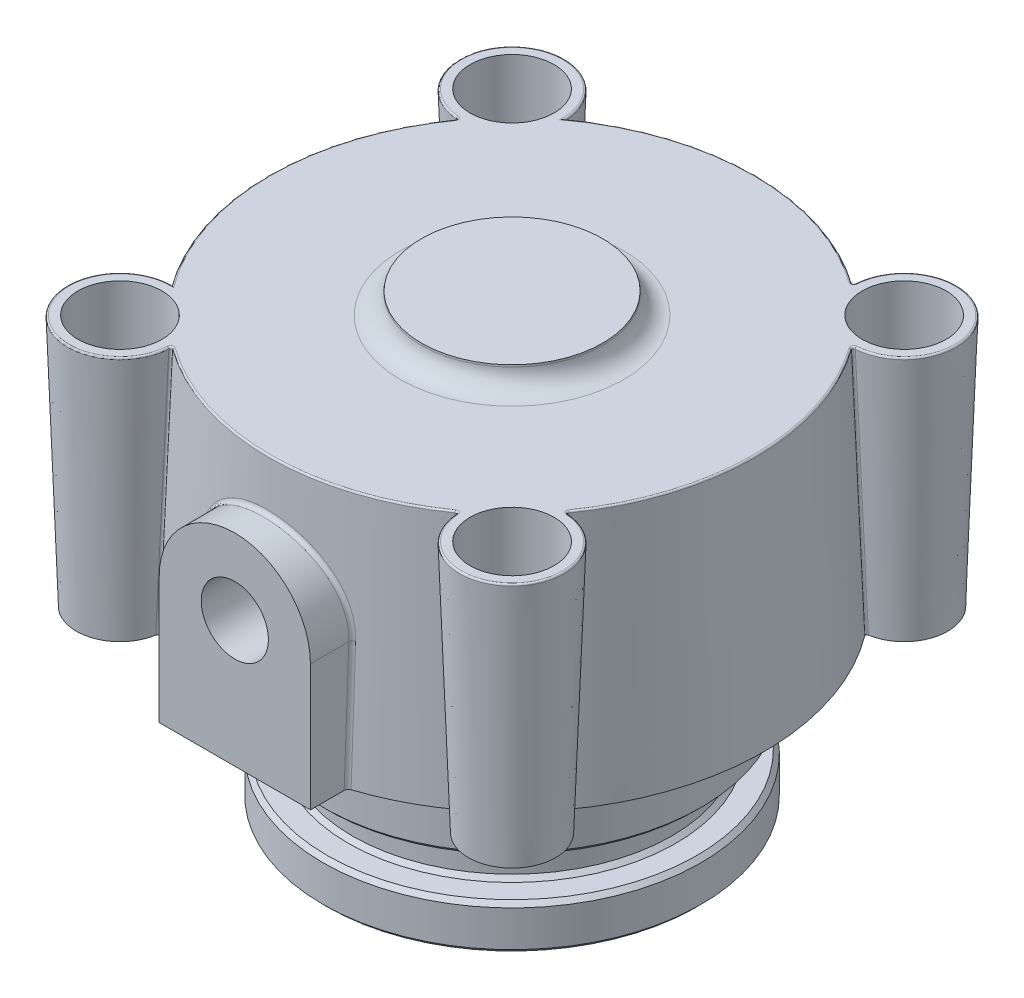
SolidWorks part; units mm, degrees
note: The reader was unsure of these and kept them because the rebuilt part matched: shared geometry of "Sketch8<4>", "Sketch8<5>", "Croquis17<2>", "Croquis1<2>".
material "Aleación 1060"
ref_plane "Front Plane" through (0, 0, 0) normal (0, 0, 1) x (1, 0, 0)
ref_plane "Top Plane" through (0, 0, 0) normal (0, 1, 0) x (1, 0, 0)
ref_plane "Right Plane" through (0, 0, 0) normal (1, 0, 0) x (0, 0, -1)
sketch "Sketch1" plane through (0, 0, 0) normal (0, 1, 0) x (1, 0, 0)
  circle A0 centre (0, 0) radius 22.5
  dimension "D1" = 45
extrude "Boss-Extrude1" add sketch "Sketch1" along normal blind 20
sketch "Sketch2" plane through (0, 20, 0) normal (0, 1, 0) x (1, 0, 0)
  circle A0 centre (0, 0) radius 30
  point P14 (0, 0)
  point P19 (0, 0)
  dimension "D1" = 60
extrude "Boss-Extrude2" add sketch "Sketch2" along normal blind 30 draft 2
sketch "Sketch3" plane through (0, 50, 0) normal (0, 1, 0) x (1, 0, 0)
  circle A0 centre (0, 0) radius 11
  dimension "D1" = 22
extrude "Boss-Extrude3" add sketch "Sketch3" along normal blind 2.5 draft 5 and the other way blind 40
ref_plane "Plane1" through (0, 0, 23) normal (0, 0, 1) x (1, 0, 0)
sketch "Sketch8" plane through (0, 0, 23) normal (0, 0, 1) x (1, 0, 0)
  line L3 (-9, 35.0488) -> (-9, 20)
  line L6 (0, -55) -> (0, 55) construction
  line L7 (28.9524, 50) -> (-28.9524, 50) construction
  line L10 (-22.5, 20) -> (22.5, 20) construction
  line L11 (-9, 20) -> (9, 20)
  line L12 (9, 20) -> (9, 35.0488)
  line L13 (-9, 20) -> (9, 20)
  arc A0 (-9, 35.0488) -> (9, 35.0488) centre (0, 35.0488) cw
  circle A1 centre (0, 35.0488) radius 4
  dimension "D3" = 9
  dimension "D4" = 8
  dimension "D1" = 18
  dimension "D6" = 14.9512
sketch "Croquis1" plane through (0, 52.5, 0) normal (0, 1, 0) x (1, 0, 0)
  circle A0 centre (0, 0) radius 8
  dimension "D1" = 16
extrude "Cortar-Extruir1" cut sketch "Croquis1" against normal blind 90
sketch "Croquis2" plane through (0, 52.5, 0) normal (0, 1, 0) x (1, 0, 0)
  circle A0 centre (0, 0) radius 9
  dimension "D1" = 18
sketch "Croquis3" plane through (0, 50, 0) normal (0, 1, 0) x (1, 0, 0)
  line L0 (0, 0) -> (-35.3676, 35.3676) construction
  line L1 (0, 0) -> (35.2874, -35.2874) construction
  line L2 (0, 0) -> (35.299, 35.299) construction
  line L3 (0, 0) -> (-35.4361, -35.4361) construction
  circle A9 centre (-23.3345, 23.3345) radius 6.235
  circle A12 centre (-23.3345, 23.3345) radius 5
  point P7 (-23.3345, 23.3345)
  point P9 (-21.2132, -21.2132)
  point P12 (21.2132, -21.2132)
  point P13 (-23.3345, 23.3345)
  point P14 (21.2132, 21.2132)
  circle M5 centre (0, 0) radius 28.9524
  dimension "D3" = 90
  dimension "D1" = 12.47
  dimension "D2" = 90
  dimension "D5" = 10
  dimension "D6" = 33
extrude "Saliente-Extruir1" add sketch "Croquis3" against normal blind 30 draft 2 contours A9 M5 | A9 A12 M5 | A12
pattern_circular "MatrizC1" count 4 over 360 about axis through (0, 0, 0) along (0, 1, 0) of "Saliente-Extruir1"
extrude "Saliente-Extruir2" add sketch "Sketch8" along normal blind 10 contours L12 A0 L3 L11 | A1
pattern_circular "MatrizC2" count 2 over 360 about axis through (0, 0, 0) along (0, 1, 0) of "Saliente-Extruir2"
cosmetic thread "Rosca cosmética1" parameters "D1"=15, "D2"=10
sketch "Croquis10" plane through (0, 0, 23) normal (0, 0, 1) x (1, 0, 0)
  circle A0 centre (0, 35.0488) radius 3.9079
ref_plane "Plano1" through (0, 0, -37) normal (0, 0, -1) x (-1, 0, 0)
sketch "Croquis11" plane through (0, 0, -37) normal (0, 0, -1) x (-1, 0, 0)
  circle A0 centre (0, 35.0488) radius 4
extrude "Cortar-Extruir5" cut sketch "Croquis11" against normal blind 40
sketch "Croquis12" plane through (0, 0, 0) normal (1, 0, 0) x (0, 0, -1)
  line L0 (-22.5, 10) -> (-19, 10)
  line L1 (-22.5, 20) -> (-22.5, 0) construction
  line L2 (-19, 10) -> (-19, 5.3)
  line L3 (-19, 5.3) -> (-22.5, 5.3)
  line L4 (0, 0) -> (0, 52.5) construction
  line L5 (9, 52.5) -> (-9, 52.5) construction
  line L6 (-22.5, 10) -> (-22.5, 5.3)
  dimension "D1" = 4.7
  dimension "D2" = 3.5
revolve "Cortar-Revolución1" cut sketch "Croquis12" angle 360 about L4
sketch "Croquis13" plane through (0, 0, 0) normal (1, 0, 0) x (0, 0, -1)
  line L0 (0.0017, 13.7509) -> (-11.9983, 13.7509)
  line L1 (-11.9983, 13.7509) -> (-11.9983, 17.8541)
  line L2 (-11.9983, 17.8541) -> (0.0017, 17.8541)
  line L3 (0.0017, 17.8541) -> (0.0017, 13.7509)
  line L5 (0, 0) -> (0, 52.5) construction
  line L6 (9, 52.5) -> (-9, 52.5) construction
  line L7 (0.0017, 17.8541) -> (0.0017, 13.7509)
  dimension "D1" = 4.1033
  dimension "D2" = 12
revolve "Cortar-Revolución3" cut sketch "Croquis13" angle 360 about L3
extrude "Cortar-Extruir7" cut sketch "Sketch8<4>" along normal blind 7 contours A1
sketch "Sketch8<4>" plane through (0, 0, 23) normal (0, 0, 1) x (1, 0, 0) same geometry as "Sketch8"
extrude "Cortar-Extruir8" cut sketch "Sketch8<5>" against normal blind 0.2 contours A1
sketch "Sketch8<5>" plane through (0, 0, 23) normal (0, 0, 1) x (1, 0, 0) same geometry as "Sketch8"
sketch "Croquis16" plane through (0, 0, 0) normal (0, -1, 0) x (1, 0, 0)
  circle A0 centre (0, 14.3104) radius 3
  point P0 (0, 14.3104)
  dimension "D1" = 6
extrude "Cortar-Extruir9" cut sketch "Croquis16" against normal blind 34
ref_plane "Plano2" through (0, 0, 15) normal (0, 0, 1) x (1, 0, 0)
sketch "Croquis17" plane through (0, 0, 15) normal (0, 0, 1) x (1, 0, 0)
  circle A0 centre (0, 35.0488) radius 3.5
  dimension "D1" = 7
extrude "Cortar-Extruir10" cut sketch "Croquis17" along normal blind 8
cosmetic thread "Rosca cosmética10" parameters "D1"=5, "D2"=7.513
extrude "Cortar-Extruir11" cut sketch "Croquis17<2>" against normal blind 0.2
sketch "Croquis17<2>" plane through (0, 0, 15) normal (0, 0, 1) x (1, 0, 0) same geometry as "Croquis17"
ref_plane "Plano3" through (0, 0, 13) normal (0, 0, 1) x (1, 0, 0)
sketch "Croquis18" plane through (0, 0, 13) normal (0, 0, 1) x (1, 0, 0)
  circle A0 centre (0, 35.0488) radius 3
  dimension "D1" = 6
extrude "Cortar-Extruir12" cut sketch "Croquis18" along normal blind 8
sketch "Croquis19" plane through (0, 0, 0) normal (0, 0, 1) x (1, 0, 0)
  circle A0 centre (0, 35.0488) radius 2.5
  dimension "D1" = 5
extrude "Cortar-Extruir13" cut sketch "Croquis19" along normal blind 20
sketch "Croquis21" plane through (0, 50, 0) normal (0, 1, 0) x (1, 0, 0)
  circle A0 centre (-23.3345, 23.3345) radius 5
  circle A1 centre (-23.3345, 23.3345) radius 2.5
  point P0 (-23.3345, 23.3345)
  point P3 (25.8804, 25.8804)
  point P5 (28.4263, -23.3345)
  point P7 (-20.7886, -25.8804)
  point P10 (2.5459, 0)
  dimension "D2" = 10
  dimension "D1" = 4
extrude "Cortar-Extruir14" cut sketch "Croquis21" against normal blind 10 contours A1 | A0 A1
pattern_circular "MatrizC3" count 4 over 360 about axis through (0, 0, 0) along (0, 1, 0) of "Cortar-Extruir14"
fillet "Redondeo8" radius 0.2 14 edges at (-28.9524, 50, 0) (-23.5243, 40.7577, -17.4253) (-27.7433, 50, -27.7433) (0, 50, 28.9524) (28.9524, 50, 0) (0, 50, -28.9524) (-17.4253, 40.7577, 23.5243) (-27.7433, 50, 27.7433) (23.5243, 40.7577, 17.4253) (17.9257, 26.8144, 23.7581) (27.7433, 50, 27.7433) (17.4253, 40.7577, -23.5243) (23.7581, 26.8144, -17.9257) (27.7433, 50, -27.7433)
chamfer "Chaflán1" distance 0.25 angle 45 1 edges at (0, 38.0488, 14.8)
sketch "Croquis24" plane through (0, 50, 0) normal (0, 1, 0) x (1, 0, 0)
  circle A0 centre (-23.3345, 23.3345) radius 3
  point P0 (-23.3345, 23.3345)
  dimension "D1" = 6
extrude "Cortar-Extruir16" cut sketch "Croquis24" against normal blind 30
sketch "Croquis25" plane through (0, 50, 0) normal (0, 1, 0) x (1, 0, 0)
  circle A1 centre (-23.3345, -23.3345) radius 3
  circle A2 centre (23.3345, -23.3345) radius 3
  circle A3 centre (23.3345, 23.3345) radius 3
  point P0 (23.3345, 23.3345)
  point P1 (-23.3345, -23.3345)
  point P3 (23.3345, -23.3345)
  dimension "D1" = 6
  dimension "D2" = 6
  dimension "D3" = 6
extrude "Cortar-Extruir17" cut sketch "Croquis25" against normal blind 30
chamfer "Chaflán3" distance 0.5 angle 45 4 edges at (0, 10, -19) (0, 10, -22.5) (0, 5.3, -22.5) (0, 5.3, -19)
fillet "Redondeo11" radius 0.5 1 edges at (0, 20, 22.5)
chamfer "Chaflán5" distance 0.2 angle 45 4 edges at (0, 17.8541, -8) (0, 17.8541, -12.0017) (0, 13.7509, -12.0017) (0, 13.7509, 8)
chamfer "Chaflán7" distance 0.5 angle 45 1 edges at (-4, 35.0488, -33)
fillet "Redondeo13" radius 0.5 3 edges at (0.7931, 44.0138, 29.1506)
fillet "Redondeo14" radius 0.5 3 edges at (-0.7931, 44.0138, -29.1506)
extrude "Boss-Extrude4" add sketch "Croquis1<2>" against normal blind 7.5
sketch "Croquis1<2>" plane through (0, 52.5, 0) normal (0, 1, 0) x (1, 0, 0) same geometry as "Croquis1"
chamfer "Chaflán8" distance 0.5 angle 45 1 edges at (0, 0, 22.5)
fillet "Redondeo16" radius 2.5 1 edges at (0, 45, 8)
fillet "Redondeo17" radius 2.5 1 edges at (0, 50, 11)
